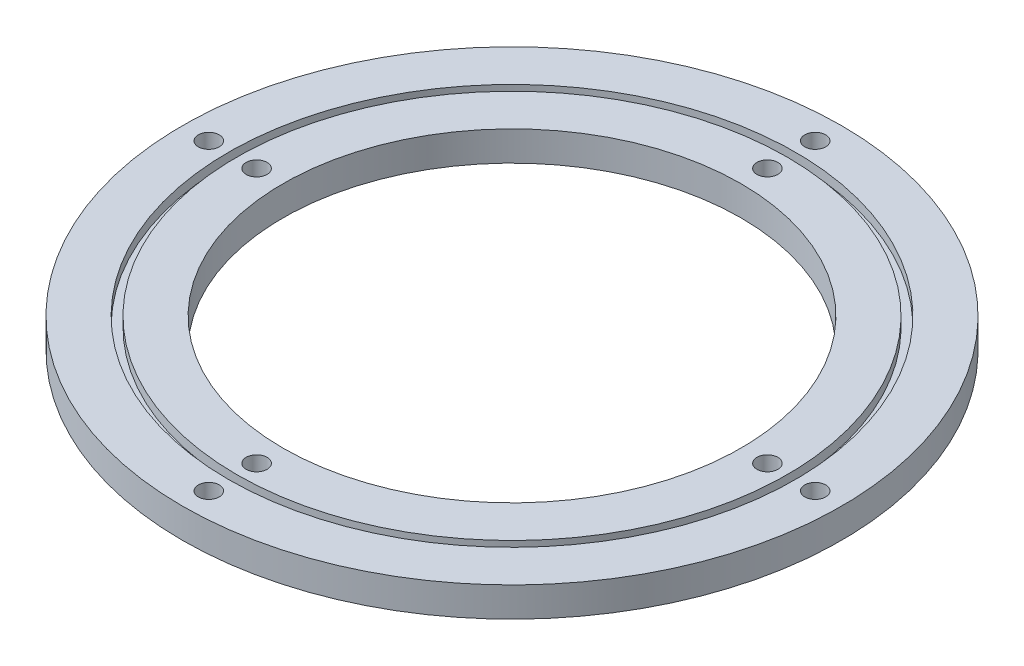
SolidWorks part; units mm, degrees
ref_plane "Front Plane" through (0, 0, 0) normal (0, 0, 1) x (1, 0, 0)
ref_plane "Top Plane" through (0, 0, 0) normal (0, 1, 0) x (1, 0, 0)
ref_plane "Right Plane" through (0, 0, 0) normal (1, 0, 0) x (0, 0, -1)
sketch "Sketch1" plane through (0, 0, 0) normal (0, 1, 0) x (1, 0, 0)
  line L0 (0, 0) -> (77.5, 0) construction
  line L1 (-69.5, 0) -> (-84.75, 0) construction
  line L2 (-84.75, 0) -> (-100, 0) construction
  line L3 (84.75, 0) -> (84.75, 53.0795) construction
  circle A0 centre (0, 0) radius 100
  circle A1 centre (0, 0) radius 69.5
  circle A2 centre (77.5, 0) radius 3.175
  circle A3 centre (0, 0) radius 84.75 construction
  circle A4 centre (0, 0) radius 86.02
  circle A5 centre (0, 0) radius 83.48
  circle A6 centre (92, 0) radius 3.175
  circle A7 centre (0, -92) radius 3.175
  circle A8 centre (0, -77.5) radius 3.175
  circle A9 centre (-92, 0) radius 3.175
  circle A10 centre (-77.5, 0) radius 3.175
  circle A11 centre (0, 92) radius 3.175
  circle A12 centre (0, 77.5) radius 3.175
  point P33 (0, 0)
  dimension "D1" = 200
  dimension "D2" = 139
  dimension "D4" = 6.35
  dimension "D7" = 4
  dimension "D3" = 77.5
  dimension "D5" = 1.27
  dimension "D6" = 1.27
extrude "Boss-Extrude1" add sketch "Sketch1" along normal mid plane 9 contours A0 A9 A6 A4 A7 A11 | A5 A12 A10 A8 A2 A1 region at (-97.1716, 0, 0) region at (-81.1188, 0, 0)
extrude "Boss-Extrude2" add sketch "Sketch1<3>" along normal mid plane 3.175 contours A4 A5 region at (-83.587, 0, 0)
sketch "Sketch1<3>" plane through (0, 0, 0) normal (0, 1, 0) x (1, 0, 0) same geometry as "Sketch1"
